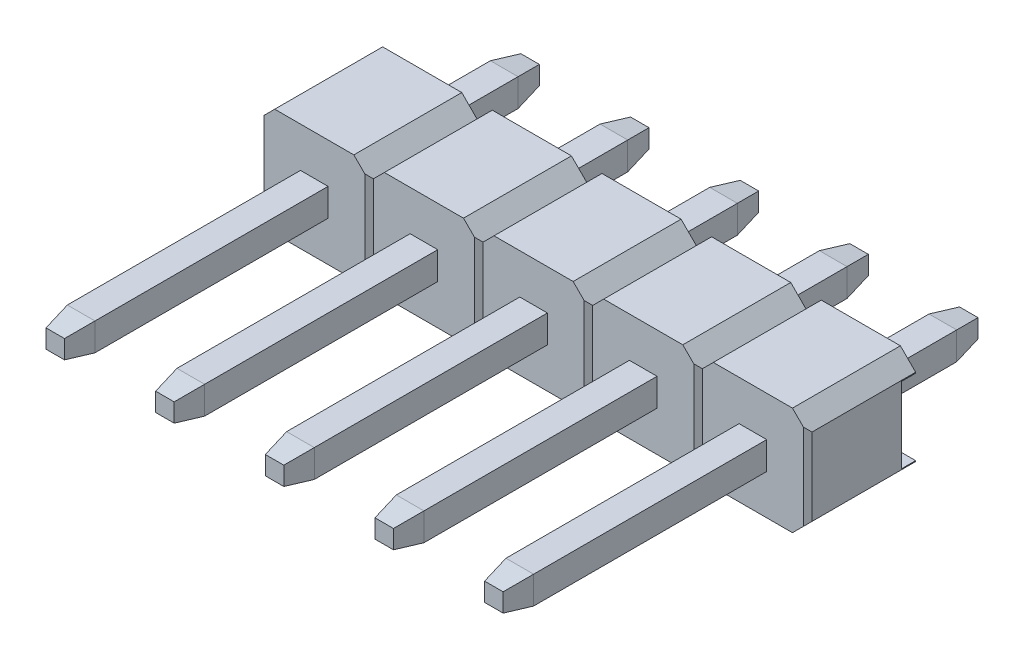
SolidWorks part; units mm, degrees
ref_plane "Front Plane" through (0, 0, 0) normal (0, 0, 1) x (1, 0, 0)
ref_plane "Top Plane" through (0, 0, 0) normal (0, 1, 0) x (1, 0, 0)
ref_plane "Right Plane" through (0, 0, 0) normal (1, 0, 0) x (0, 0, -1)
sketch "Sketch1" plane through (0, 0, 0) normal (0, 0, 1) x (1, 0, 0)
  line L0 (-1.27, 0.8964) -> (-0.9164, 1.25)
  line L1 (-0.9164, 1.25) -> (0.9164, 1.25)
  line L2 (-1.27, 0.8964) -> (-1.27, -0.8964)
  line L3 (-0.9164, -1.25) -> (0.9164, -1.25)
  line L4 (1.27, 0.8964) -> (1.27, -0.8964)
  line L5 (-1.27, -0.8964) -> (-0.9164, -1.25)
  line L6 (0.9164, -1.25) -> (1.27, -0.8964)
  line L7 (1.27, 0.8964) -> (0.9164, 1.25)
  point P0 (1.27, -1.25)
  point P7 (-1.27, 1.25)
  point P10 (-1.27, -1.25)
  point P15 (1.27, 1.25)
  dimension "D5" = 0.25
  dimension "D1" = 2.54
  dimension "D2" = 2.5
  dimension "D3" = 1.27
  dimension "D4" = 1.25
  dimension "D6" = 0.25
  dimension "D7" = 0.25
  dimension "D8" = 0.25
extrude "Extrude1" add sketch "Sketch1" along normal blind 1.25 and the other way blind 1.25
sketch "Sketch4" plane through (0, 0, 0) normal (0, 1, 0) x (1, 0, 0)
  line L0 (-1.27, -1.15) -> (-1.17, -1.25)
  line L1 (-1.17, -1.25) -> (-1.27, -1.25)
  line L2 (-1.27, -1.25) -> (-1.27, -1.15)
  line L3 (1.17, -1.25) -> (1.27, -1.15)
  line L4 (1.27, -1.15) -> (1.27, -1.25)
  line L5 (1.27, -1.25) -> (1.17, -1.25)
extrude "Cut-Extrude3" cut sketch "Sketch4" against normal through all and the other way through all
pattern_linear "LPattern4" count 5 spacing 2.54 along (-1, 0, 0) of "Extrude1", "Cut-Extrude3"
sketch "Sketch2" plane through (0, 0, 0) normal (1, 0, 0) x (0, -1, 0)
  line L1 (-0.8764, 1.25) -> (0.8764, 1.25)
  line L2 (-0.8764, 1.25) -> (-0.8764, 0.92)
  line L3 (-0.8764, 0.92) -> (0.8764, 0.92)
  line L4 (0.8764, 1.25) -> (0.8764, 0.92)
  dimension "D1" = 0.33
extrude "Cut-Extrude1" cut sketch "Sketch2" against normal through all and the other way through all
sketch "Sketch3" plane through (0, 0, 0) normal (1, 0, 0) x (0, 0, -1)
  line L0 (-7.25, 0) -> (3.75, 0)
  line L1 (1.25, 1.25) -> (1.25, 0.8964) construction
  dimension "D1" = 6
  dimension "D2" = 2.5
extrude "Extrude-Thin1" add sketch "Sketch3" along normal blind 0.32 and the other way blind 0.32 thin thin type mid plane wall 0.64
pattern_linear "LPattern5" count 1 spacing 2.54 along (1, 0, 0) count 5 spacing 2.54 along (-1, 0, 0) of "Extrude-Thin1"
chamfer "Chamfer2" distance 0.6 angle 10 40 edges at (0.32, 0, 7.25) (0, -0.32, 7.25) (-0.32, 0, 7.25) (0, 0.32, 7.25) (0.32, 0, -3.75) (-0.32, 0, -3.75) (-4.76, 0, -3.75) (-5.4, 0, -3.75) (-2.22, 0, -3.75) (-2.86, 0, -3.75) (-2.22, 0, 7.25) (-2.54, -0.32, 7.25) (-2.86, 0, 7.25) (-2.54, 0.32, 7.25) (-4.76, 0, 7.25) (-5.08, -0.32, 7.25) (-5.4, 0, 7.25) (-5.08, 0.32, 7.25) (-2.54, 0.32, -3.75) (-2.54, -0.32, -3.75) (0, 0.32, -3.75) (0, -0.32, -3.75) (-9.84, 0, -3.75) (-10.16, 0.32, -3.75) (-10.48, 0, -3.75) (-10.16, -0.32, -3.75) (-7.3, 0, -3.75) (-7.62, 0.32, -3.75) (-7.94, 0, -3.75) (-7.62, -0.32, -3.75) (-5.08, 0.32, -3.75) (-5.08, -0.32, -3.75) (-9.84, 0, 7.25) (-10.16, -0.32, 7.25) (-10.48, 0, 7.25) (-10.16, 0.32, 7.25) (-7.3, 0, 7.25) (-7.62, -0.32, 7.25) (-7.94, 0, 7.25) (-7.62, 0.32, 7.25) first distance on face at (0.32, 0, 4.25) first distance on face at (0, -0.32, 4.25) first distance on face at (-0.32, 0, 4.25) first distance on face at (0, 0.32, 4.25) first distance on face at (0.32, 0, -2.335) first distance on face at (-0.32, 0, -2.335) first distance on face at (-4.76, 0, -2.335) first distance on face at (-5.4, 0, -2.335) first distance on face at (-2.22, 0, -2.335) first distance on face at (-2.86, 0, -2.335) first distance on face at (-2.22, 0, 4.25) first distance on face at (-2.54, -0.32, 4.25) first distance on face at (-2.86, 0, 4.25) first distance on face at (-2.54, 0.32, 4.25) first distance on face at (-4.76, 0, 4.25) first distance on face at (-5.08, -0.32, 4.25) first distance on face at (-5.4, 0, 4.25) first distance on face at (-5.08, 0.32, 4.25) first distance on face at (-2.54, 0.32, -2.335) first distance on face at (-2.54, -0.32, -2.335) first distance on face at (0, 0.32, -2.335) first distance on face at (0, -0.32, -2.335) first distance on face at (-9.84, 0, -2.335) first distance on face at (-10.16, 0.32, -2.335) first distance on face at (-10.48, 0, -2.335) first distance on face at (-10.16, -0.32, -2.335) first distance on face at (-7.3, 0, -2.335) first distance on face at (-7.62, 0.32, -2.335) first distance on face at (-7.94, 0, -2.335) first distance on face at (-7.62, -0.32, -2.335) first distance on face at (-5.08, 0.32, -2.335) first distance on face at (-5.08, -0.32, -2.335) first distance on face at (-9.84, 0, 4.25) first distance on face at (-10.16, -0.32, 4.25) first distance on face at (-10.48, 0, 4.25) first distance on face at (-10.16, 0.32, 4.25) first distance on face at (-7.3, 0, 4.25) first distance on face at (-7.62, -0.32, 4.25) first distance on face at (-7.94, 0, 4.25) first distance on face at (-7.62, 0.32, 4.25)
ref_plane "Board Plane" through (0, 0, -1.5) normal (0, 0, 1) x (1, 0, 0)
sketch "Component_Outline" plane through (0, 0, -1.5) normal (0, 0, 1) x (1, 0, 0)
  line L0 (1.27, 0.8964) -> (1.27, -0.8964)
  line L1 (1.27, -0.8964) -> (0.9164, -1.25)
  line L2 (0.9164, -1.25) -> (-0.9164, -1.25)
  line L3 (-0.9164, -1.25) -> (-1.27, -0.8964)
  line L4 (-1.27, -0.8964) -> (-1.6236, -1.25)
  line L5 (-1.6236, -1.25) -> (-3.4564, -1.25)
  line L6 (-3.4564, -1.25) -> (-3.81, -0.8964)
  line L7 (-3.81, -0.8964) -> (-4.1636, -1.25)
  line L8 (-4.1636, -1.25) -> (-5.9964, -1.25)
  line L9 (-5.9964, -1.25) -> (-6.35, -0.8964)
  line L10 (-6.35, -0.8964) -> (-6.7036, -1.25)
  line L11 (-6.7036, -1.25) -> (-8.5364, -1.25)
  line L12 (-8.5364, -1.25) -> (-8.89, -0.8964)
  line L13 (-8.89, -0.8964) -> (-9.2436, -1.25)
  line L14 (-9.2436, -1.25) -> (-11.0764, -1.25)
  line L15 (-11.0764, -1.25) -> (-11.43, -0.8964)
  line L16 (-11.43, -0.8964) -> (-11.43, 0.8964)
  line L17 (-11.43, 0.8964) -> (-11.0764, 1.25)
  line L18 (-11.0764, 1.25) -> (-9.2436, 1.25)
  line L19 (-9.2436, 1.25) -> (-8.89, 0.8964)
  line L20 (-8.89, 0.8964) -> (-8.5364, 1.25)
  line L21 (-8.5364, 1.25) -> (-6.7036, 1.25)
  line L22 (-6.7036, 1.25) -> (-6.35, 0.8964)
  line L23 (-6.35, 0.8964) -> (-5.9964, 1.25)
  line L24 (-5.9964, 1.25) -> (-4.1636, 1.25)
  line L25 (-4.1636, 1.25) -> (-3.81, 0.8964)
  line L26 (-3.81, 0.8964) -> (-3.4564, 1.25)
  line L27 (-3.4564, 1.25) -> (-1.6236, 1.25)
  line L28 (-1.6236, 1.25) -> (-1.27, 0.8964)
  line L29 (-1.27, 0.8964) -> (-0.9164, 1.25)
  line L30 (-0.9164, 1.25) -> (0.9164, 1.25)
  line L31 (0.9164, 1.25) -> (1.27, 0.8964)
  point P64 (0, 0)
